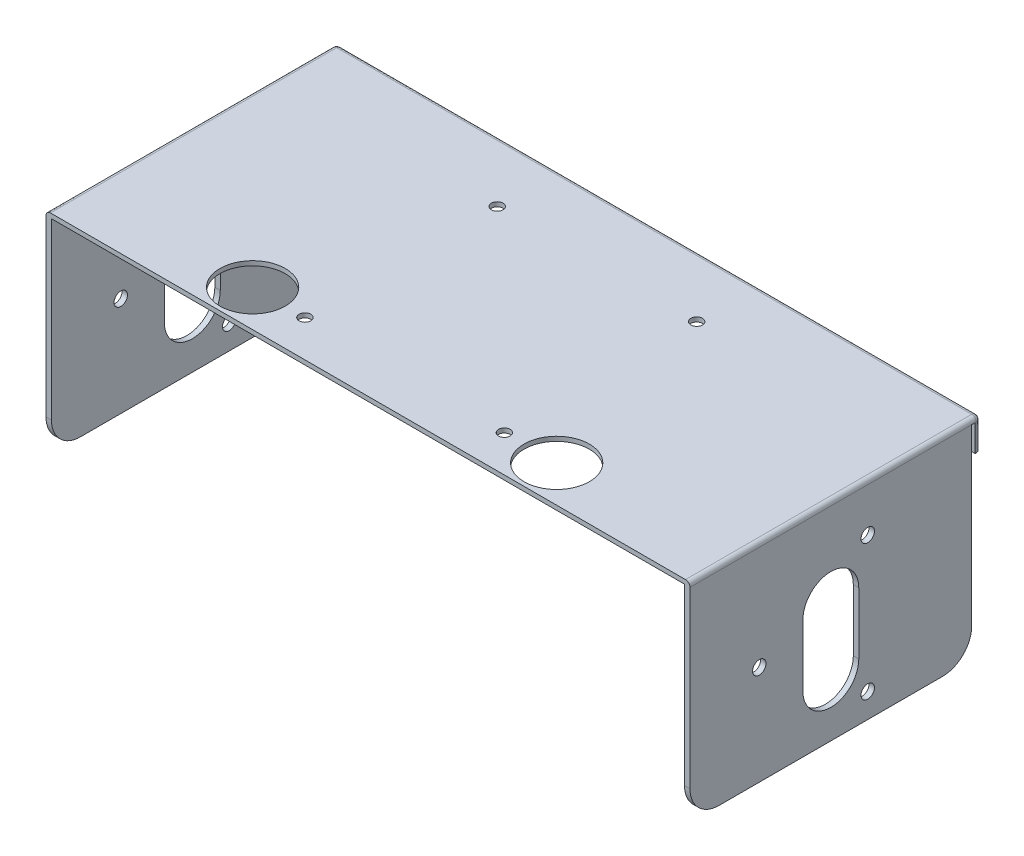
SolidWorks part; units mm, degrees
ref_plane "Plan de face" through (0, 0, 0) normal (0, 0, 1) x (1, 0, 0)
ref_plane "Plan de dessus" through (0, 0, 0) normal (0, 1, 0) x (1, 0, 0)
ref_plane "Plan de droite" through (0, 0, 0) normal (1, 0, 0) x (0, 0, -1)
sketch "Esquisse2" plane through (0, 0, 0) normal (0, 1, 0) x (1, 0, 0)
  line L0 (-72, 0) -> (72, 0)
  line L1 (-72, 0) -> (-72, 65)
  line L2 (-72, 65) -> (72, 65)
  line L3 (72, 65) -> (72, 0)
  point P3 (0, 0)
  dimension "D1" = 144
  dimension "D2" = 65
extrude "Boss.-Extru.1" add sketch "Esquisse2" along normal blind 1
sketch "Esquisse3" plane through (0, 0, 0) normal (0, -1, 0) x (1, 0, 0)
  line L0 (-72, -65) -> (-72, -63.78)
  line L1 (72, -65) -> (-72, -65) construction
  line L2 (-72, -63.78) -> (72, -63.78)
  line L3 (72, -63.78) -> (72, -65)
  line L6 (-72, -65) -> (72, -65)
  line L7 (-72, -65) -> (-72, 0) construction
  line L8 (72, 0) -> (72, -65) construction
  dimension "D1" = 1.22
extrude "Boss.-Extru.2" add sketch "Esquisse3" along normal blind 6
sketch "Esquisse6" plane through (0, 0, 0) normal (0, -1, 0) x (-1, 0, 0)
  line L0 (70.78, 0) -> (70.78, 63)
  line L1 (72, 0) -> (-72, 0) construction
  line L2 (70.78, 63) -> (72, 63)
  line L3 (72, 63.78) -> (72, 0) construction
  line L4 (72, 63) -> (72, 0)
  line L5 (72, 0) -> (70.78, 0)
  line L6 (-72, 0) -> (-72, 63)
  line L7 (-72, 0) -> (-72, 63.78) construction
  line L8 (-72, 63) -> (-70.78, 63)
  line L9 (-70.78, 63) -> (-70.78, 0)
  line L10 (-70.78, 0) -> (-72, 0)
  line L11 (72, 65) -> (-72, 65) construction
  dimension "D1" = 2
  dimension "D2" = 2
  dimension "D3" = 1.22
  dimension "D4" = 1.22
extrude "Boss.-Extru.4" add sketch "Esquisse6" along normal blind 45.5
fillet "Congé3" radius 1 1 edges at (0, 1, -65)
fillet "Congé4" radius 1 6 edges at (-72, -3, -65) (-72, 0.7071, -64.7071) (72, -3, -65) (72, 0.7071, -64.7071) (-72, 1, -32) (72, 1, -32)
sketch "Esquisse7" plane through (72, 0, 0) normal (1, 0, 0) x (0, 0, -1)
  line L0 (0, -45.5) -> (0, -39)
  line L1 (0, 0) -> (0, -45.5) construction
  line L2 (0, -45.5) -> (6.5, -45.5)
  line L3 (63, -45.5) -> (0, -45.5) construction
  line L4 (56.5, -45.5) -> (63, -45.5)
  line L5 (63, -45.5) -> (63, -39)
  line L6 (63, -45.5) -> (63, 0) construction
  arc A0 (0, -39) -> (6.5, -45.5) centre (6.5, -39) ccw
  arc A1 (63, -39) -> (56.5, -45.5) centre (56.5, -39) cw
  dimension "D1" = 6.5
  dimension "D2" = 6.5
extrude "Enlèv. mat.-Extru.2" cut sketch "Esquisse7" against normal through all
sketch "Esquisse8" plane through (0, 1, 0) normal (0, 1, 0) x (1, 0, 0)
  line L0 (-71, 64) -> (-71, 0) construction
  line L1 (71, 0) -> (71, 64) construction
  line L2 (-71, 0) -> (71, 0) construction
  circle A0 centre (-34, 8.2) radius 7.3
  circle A1 centre (34, 8.2) radius 7.3
  dimension "D3" = 14.6
  dimension "D4" = 8.2
  dimension "D1" = 37
  dimension "D2" = 37
extrude "Enlèv. mat.-Extru.3" cut sketch "Esquisse8" against normal through all
sketch "Esquisse9" plane through (0, 1, 0) normal (0, 1, 0) x (1, 0, 0)
  line L0 (-22.3, 51.2) -> (22.3, 51.2) construction
  line L1 (-71, 0) -> (71, 0) construction
  circle A0 centre (-22.3, 8.2) radius 1.3
  circle A1 centre (22.3, 8.2) radius 1.3
  circle A2 centre (-34, 8.2) radius 7.3 construction
  circle A3 centre (34, 8.2) radius 7.3 construction
  circle A4 centre (-22.3, 51.2) radius 1.3
  circle A5 centre (22.3, 51.2) radius 1.3
  dimension "D3" = 8.2
  dimension "D1" = 11.7
  dimension "D2" = 11.7
  dimension "D4" = 43
extrude "Enlèv. mat.-Extru.4" cut sketch "Esquisse9" against normal through all
sketch "Esquisse10" plane through (72, 0, 0) normal (1, 0, 0) x (0, 0, -1)
  line L0 (31.5, -32.75) -> (31.5, -18.95) construction
  line L1 (25.25, -32.75) -> (25.25, -18.95)
  line L2 (37.75, -32.75) -> (37.75, -18.95)
  line L4 (56.5, -45.5) -> (6.5, -45.5) construction
  line L5 (0, 1) -> (64, 1) construction
  arc A0 (25.25, -32.75) -> (37.75, -32.75) centre (31.5, -32.75) ccw
  arc A1 (37.75, -18.95) -> (25.25, -18.95) centre (31.5, -18.95) ccw
  point P2 (31.5, -25.85)
  point P9 (31.5, -45.5)
  point P10 (31.5, -12.7)
  point P11 (31.5, -39)
  dimension "D4" = 13.7
  dimension "D1" = 12.5
  dimension "D2" = 12.5
  dimension "D3" = 26.3
extrude "Enlèv. mat.-Extru.6" cut sketch "Esquisse10" against normal through all
sketch "Esquisse11" plane through (72, 0, 0) normal (1, 0, 0) x (0, 0, -1)
  line L0 (0, 0) -> (0, -39) construction
  line L1 (63, -39) -> (63, 0) construction
  line L2 (56.5, -45.5) -> (6.5, -45.5) construction
  line L3 (0, 1) -> (64, 1) construction
  circle A0 centre (39.75, -40.05) radius 1.5
  circle A1 centre (39.75, -9.75) radius 1.5
  circle A2 centre (15.5, -23.25) radius 1.5
  dimension "D2" = 3
  dimension "D4" = 3
  dimension "D7" = 3
  dimension "D1" = 5.45
  dimension "D3" = 23.25
  dimension "D5" = 10.75
  dimension "D6" = 24.25
  dimension "D8" = 15.5
extrude "Enlèv. mat.-Extru.7" cut sketch "Esquisse11" against normal through all
